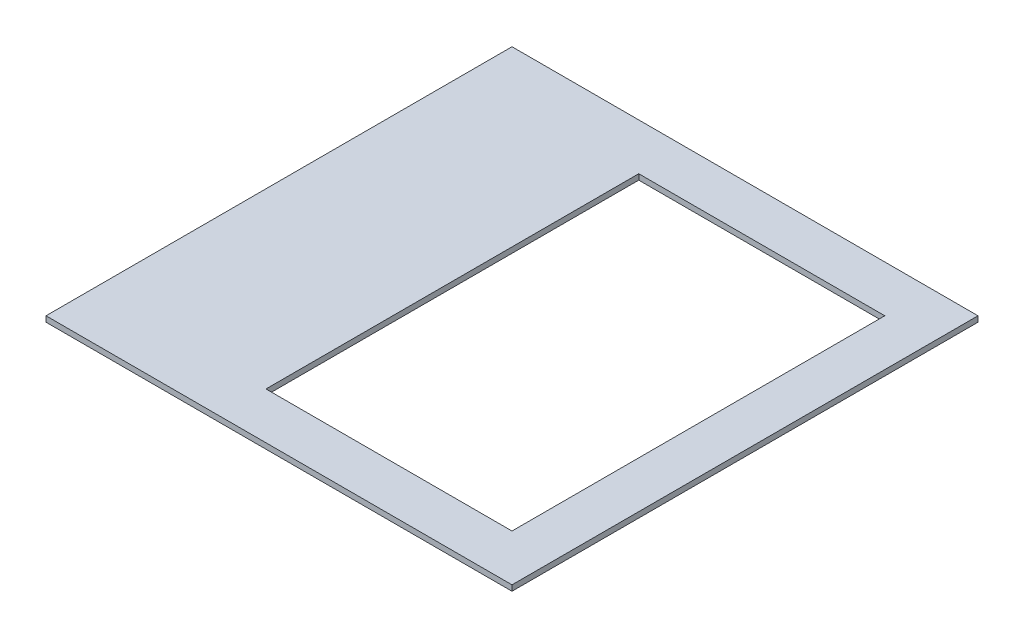
SolidWorks part; units mm, degrees
ref_plane "Спереди" through (0, 0, 0) normal (0, 0, 1) x (1, 0, 0)
ref_plane "Сверху" through (0, 0, 0) normal (0, 1, 0) x (1, 0, 0)
ref_plane "Справа" through (0, 0, 0) normal (1, 0, 0) x (0, 0, -1)
sketch "Эскиз1" plane through (0, 0, 0) normal (0, 1, 0) x (1, 0, 0)
  line L1 (-125, -125) -> (125, -125)
  line L2 (-125, -125) -> (-125, 125)
  line L3 (-125, 125) -> (125, 125)
  line L4 (125, -125) -> (125, 125)
  line L5 (-125, -125) -> (125, 125) construction
  line L6 (-125, 125) -> (125, -125) construction
  point P0 (0, 0)
  dimension "D1" = 250
  dimension "D2" = 250
extrude "Бобышка-Вытянуть1" add sketch "Эскиз1" along normal blind 3
sketch "Эскиз3" plane through (0, 0, 0) normal (0, -1, 0) x (1, 0, 0)
  line L0 (-125, -125) -> (-125, 125) construction
  line L1 (-32, 100) -> (100, 100)
  line L2 (-32, 100) -> (-32, -100)
  line L3 (-32, -100) -> (100, -100)
  line L4 (100, 100) -> (100, -100)
  line L5 (-32, 100) -> (100, -100) construction
  line L6 (-32, -100) -> (100, 100) construction
  line L7 (125, -125) -> (-125, -125) construction
  line L8 (-125, 125) -> (125, 125) construction
  line L9 (125, 125) -> (125, -125) construction
  point P0 (34, 0)
  dimension "D1" = 93
  dimension "D2" = 25
  dimension "D3" = 25
  dimension "D4" = 25
extrude "Вырез-Вытянуть1" cut sketch "Эскиз3" against normal blind 10
